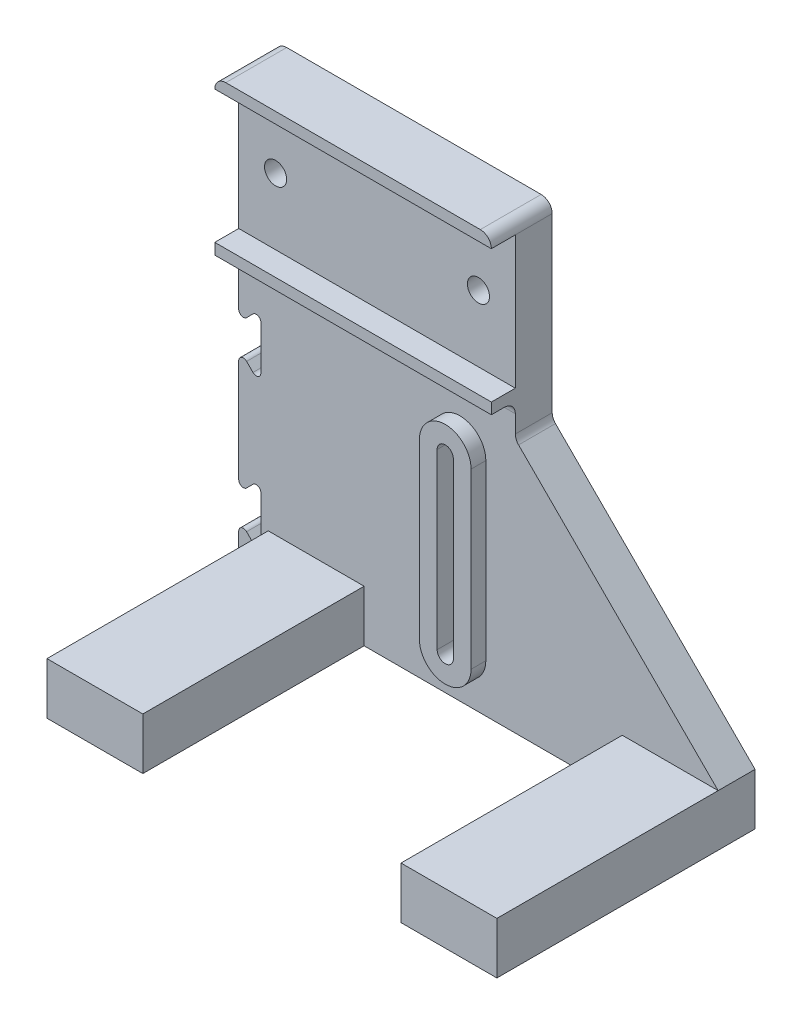
SolidWorks part; units mm, degrees
material "PET"
ref_plane "Front Plane" through (0, 0, 0) normal (0, 0, 1) x (1, 0, 0)
ref_plane "Top Plane" through (0, 0, 0) normal (0, 1, 0) x (1, 0, 0)
ref_plane "Right Plane" through (0, 0, 0) normal (1, 0, 0) x (0, 0, -1)
sketch "Sketch2" plane through (0, 0, 0) normal (0, 0, 1) x (1, 0, 0)
  line L0 (0, 0) -> (130, 0)
  line L1 (130, 0) -> (130, 14)
  line L2 (130, 14) -> (75, 69)
  line L3 (75, 69) -> (75, 120)
  line L4 (75, 120) -> (0, 120)
  line L5 (0, 120) -> (0, 0)
  dimension "D1" = 120
  dimension "D2" = 75
  dimension "D3" = 14
  dimension "D4" = 55
  dimension "D5" = 130
extrude "Boss-Extrude1" add sketch "Sketch2" against normal blind 10
sketch "Sketch3" plane through (0, 0, 0) normal (0, 0, 1) x (1, 0, 0)
  line L0 (75, 69) -> (75, 120) construction
  line L1 (0, 120) -> (75, 120)
  line L2 (0, 120) -> (0, 117)
  line L3 (0, 117) -> (75, 117)
  line L4 (75, 120) -> (75, 117)
  line L5 (0, 120) -> (75, 117) construction
  line L6 (0, 117) -> (75, 120) construction
  line L7 (0, 120) -> (0, 0) construction
  line L8 (0, 81) -> (75, 81)
  line L9 (0, 81) -> (0, 78)
  line L10 (0, 78) -> (75, 78)
  line L11 (75, 81) -> (75, 78)
  line L12 (0, 81) -> (75, 78) construction
  line L13 (0, 78) -> (75, 81) construction
  point P4 (37.5, 118.5)
  point P12 (37.5, 79.5)
  dimension "D1" = 3
  dimension "D2" = 36
extrude "Boss-Extrude2" add sketch "Sketch3" along normal blind 6.5
sketch "Sketch4" plane through (0, 0, 0) normal (0, 0, 1) x (1, 0, 0)
  line L0 (0, 99) -> (75, 99) construction
  line L1 (0, 117) -> (0, 81) construction
  line L2 (75, 81) -> (75, 117) construction
  circle A0 centre (10, 99) radius 3
  circle A1 centre (65, 99) radius 3
  dimension "D1" = 10
  dimension "D3" = 6
  dimension "D2" = 10
extrude "Cut-Extrude2" cut sketch "Sketch4" against normal up to surface (10 mm away) up to face at (68.3333, 53.8333, -10)
sketch "Sketch5" plane through (0, 0, 0) normal (0, 0, 1) x (1, 0, 0)
  line L0 (0, 0) -> (130, 0) construction
  line L1 (130, 14) -> (104, 14)
  line L2 (130, 14) -> (130, 0)
  line L3 (130, 0) -> (104, 0)
  line L4 (104, 14) -> (104, 0)
  line L5 (130, 14) -> (104, 0) construction
  line L6 (130, 0) -> (104, 14) construction
  line L7 (69, 0) -> (69, 120) construction
  line L8 (75, 120) -> (0, 120) construction
  line L9 (8, 0) -> (34, 0)
  line L10 (34, 14) -> (34, 0)
  line L11 (8, 14) -> (34, 14)
  line L12 (8, 14) -> (8, 0)
  line L13 (0, 78) -> (0, 0) construction
  point P4 (117, 7)
  dimension "D1" = 26
  dimension "D2" = 8
extrude "Boss-Extrude3" add sketch "Sketch5" along normal blind 60
sketch "Sketch6" plane through (0, 0, 0) normal (0, 0, 1) x (1, 0, 0)
  line L0 (0, 16) -> (6, 16) construction
  line L1 (0, 78) -> (0, 0) construction
  line L2 (0, 13) -> (6, 7)
  line L3 (6, 7) -> (6, 25)
  line L4 (6, 25) -> (0, 19)
  line L5 (8, 0) -> (34, 0) construction
  line L6 (0, 19) -> (0, 13)
  line L7 (0, 36) -> (-23.6105, 36) construction
  line L8 (0, 56) -> (6, 56) construction
  line L9 (6, 47) -> (0, 53)
  line L10 (6, 65) -> (6, 47)
  line L11 (0, 59) -> (6, 65)
  line L12 (0, 53) -> (0, 59)
  dimension "D1" = 6
  dimension "D2" = 6
  dimension "D3" = 16
  dimension "D4" = 6
  dimension "D5" = 40
sketch "Sketch7" plane through (0, 0, 0) normal (0, 0, 1) x (1, 0, 0)
  line L0 (60, 0) -> (60, 120) construction
  line L1 (34, 0) -> (104, 0) construction
  line L2 (75, 120) -> (0, 120) construction
  line L3 (60, 13) -> (60, 60) construction
  line L4 (53, 13) -> (53, 60)
  line L5 (67, 13) -> (67, 60)
  arc A0 (53, 13) -> (67, 13) centre (60, 13) ccw
  arc A1 (67, 60) -> (53, 60) centre (60, 60) ccw
  point P4 (60, 36.5)
  point P14 (60, 6)
  point P15 (60, 67)
  dimension "D1" = 26
  dimension "D2" = 7
  dimension "D3" = 6
extrude "Boss-Extrude5" add sketch "Sketch7" along normal blind 4
sketch "Sketch8" plane through (0, 0, 4) normal (0, 0, 1) x (1, 0, 0)
  line L4 (62.2, 13) -> (62.2, 60)
  line L5 (57.8, 60) -> (57.8, 13)
  line L6 (62.2, 13) -> (62.2, 60)
  line L7 (57.8, 60) -> (57.8, 13)
  arc A4 (57.8, 13) -> (62.2, 13) centre (60, 13) ccw
  arc A5 (62.2, 60) -> (57.8, 60) centre (60, 60) ccw
  arc A6 (57.8, 13) -> (62.2, 13) centre (60, 13) ccw
  arc A7 (62.2, 60) -> (57.8, 60) centre (60, 60) ccw
  dimension "D1" = 4.8
extrude "Cut-Extrude3" cut sketch "Sketch8" against normal through all
fillet "Fillet2" radius 3 4 edges at (75, 120, -1.75) (0, 120, -1.75) (37.5, 78, 0) (75, 69, -5)
extrude "Cut-Extrude4" cut sketch "Sketch6" against normal through all
fillet "Fillet3" radius 1.25 8 edges at (6, 25, -5) (6, 7, -5) (0, 13, -5) (0, 19, -5) (6, 47, -5) (0, 53, -5) (6, 65, -5) (0, 59, -5)
